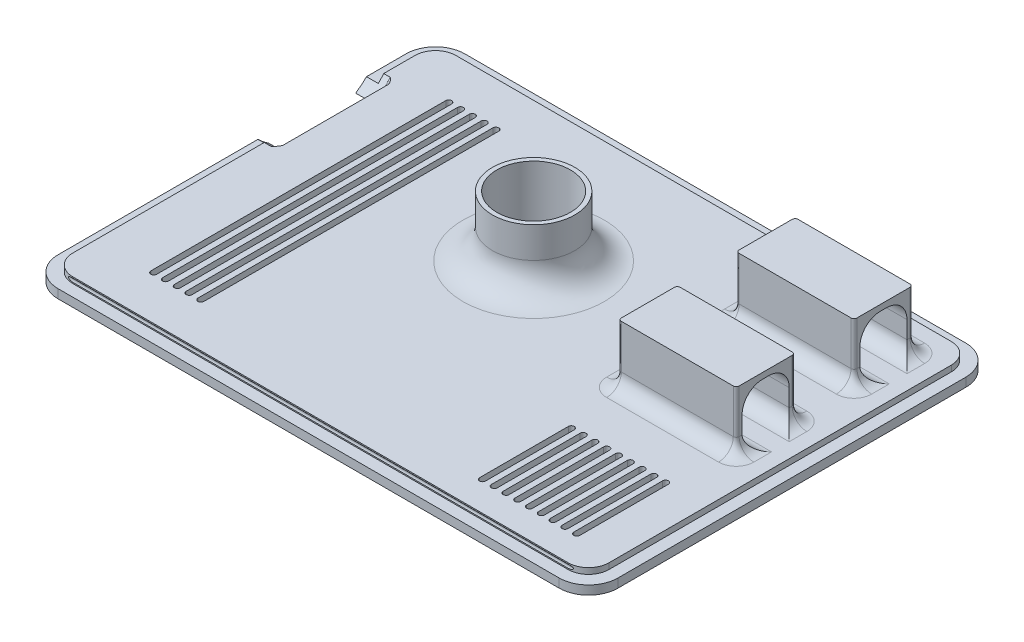
SolidWorks part; units mm, degrees
ref_plane "Front Plane" through (0, 0, 0) normal (0, 0, 1) x (1, 0, 0)
ref_plane "Top Plane" through (0, 0, 0) normal (0, 1, 0) x (1, 0, 0)
ref_plane "Right Plane" through (0, 0, 0) normal (1, 0, 0) x (0, 0, -1)
sketch "Sketch1" plane through (0, 0, 0) normal (0, 1, 0) x (1, 0, 0)
  line L0 (-95.075, -69.075) -> (95.075, -69.075)
  line L7 (95.075, -69.075) -> (95.075, 69.075)
  line L8 (-95.075, 69.075) -> (95.075, 69.075)
  line L9 (-95.075, -69.075) -> (-95.075, 69.075)
  point P0 (0, 69.075)
  point P2 (-95.075, 0)
  dimension "D1" = 138.15
  dimension "D2" = 190.15
extrude "Lid" add sketch "Sketch1" along normal blind 3
sketch "Sketch2" plane through (0, 3, 0) normal (0, 1, 0) x (1, 0, 0)
  line L0 (-91.075, 65.075) -> (-91.075, -65.075)
  line L1 (-91.075, -65.075) -> (91.075, -65.075)
  line L2 (91.075, -65.075) -> (91.075, 65.075)
  line L3 (91.075, 65.075) -> (-91.075, 65.075)
  line L4 (-95.075, 69.075) -> (-95.075, -69.075)
  line L5 (-95.075, -69.075) -> (95.075, -69.075)
  line L6 (95.075, -69.075) -> (95.075, 69.075)
  line L7 (95.075, 69.075) -> (-95.075, 69.075)
  line L8 (-95.075, 69.075) -> (-95.075, -69.075)
  line L9 (-95.075, -69.075) -> (95.075, -69.075)
  line L10 (95.075, -69.075) -> (95.075, 69.075)
  line L11 (95.075, 69.075) -> (-95.075, 69.075)
  dimension "D1" = 0
  dimension "D2" = 4
extrude "Insert" add sketch "Sketch2" along normal blind 2 contours L0 L1 L2 L3
sketch "Sketch3" plane through (0, 5, 0) normal (0, 1, 0) x (1, 0, 0)
  line L1 (41.075, 35.075) -> (81.075, 35.075)
  line L2 (41.075, 35.075) -> (41.075, 55.075)
  line L3 (41.075, 55.075) -> (81.075, 55.075)
  line L4 (91.075, 65.075) -> (-91.075, 65.075)
  line L5 (-91.075, 65.075) -> (-91.075, -65.075)
  line L6 (-91.075, -65.075) -> (91.075, -65.075)
  line L7 (91.075, -65.075) -> (91.075, 65.075)
  line L8 (91.075, 65.075) -> (-91.075, 65.075)
  line L9 (-91.075, 65.075) -> (-91.075, -65.075)
  line L10 (-91.075, -65.075) -> (91.075, -65.075)
  line L11 (91.075, -65.075) -> (91.075, 65.075)
  line L12 (81.075, 35.075) -> (81.075, 55.075)
  line L13 (41.075, 35.075) -> (81.075, 55.075) construction
  line L14 (41.075, 55.075) -> (81.075, 35.075) construction
  line L15 (41.075, 15.075) -> (81.075, 15.075)
  line L16 (41.075, 15.075) -> (41.075, -4.925)
  line L17 (41.075, -4.925) -> (81.075, -4.925)
  line L18 (81.075, 15.075) -> (81.075, -4.925)
  line L19 (41.075, 15.075) -> (81.075, -4.925) construction
  line L20 (41.075, -4.925) -> (81.075, 15.075) construction
  point P2 (61.075, 45.075)
  point P17 (61.075, 5.075)
  dimension "D2" = 10
  dimension "D3" = 50
  dimension "D4" = 10
  dimension "D5" = 30
  dimension "D6" = 50
  dimension "D7" = 70
  dimension "D1" = 0
extrude "Battery Contacts" add sketch "Sketch3" along normal blind 19.9 contours L2 L1 L12 L3 | L16 L15 L18 L17
sketch "Sketch9" plane through (81.075, 0, 0) normal (1, 0, 0) x (0, 0, -1)
  line L0 (-4.925, 5) -> (15.075, 5) construction
  line L1 (53.075, 5) -> (53.075, 15.9)
  line L2 (15.075, 24.9) -> (-4.925, 24.9) construction
  line L3 (53.075, 5) -> (37.075, 5)
  line L4 (35.075, 5) -> (55.075, 5) construction
  line L5 (37.075, 5) -> (37.075, 15.9)
  line L6 (55.075, 24.9) -> (35.075, 24.9) construction
  line L7 (46.075, 22.9) -> (44.075, 22.9)
  line L8 (-4.925, 5) -> (15.075, 5)
  line L9 (15.075, 5) -> (15.075, 24.9)
  line L10 (15.075, 24.9) -> (-4.925, 24.9)
  line L11 (-4.925, 24.9) -> (-4.925, 5)
  line L12 (35.075, 5) -> (55.075, 5)
  line L13 (55.075, 5) -> (55.075, 24.9)
  line L14 (55.075, 24.9) -> (35.075, 24.9)
  line L15 (35.075, 24.9) -> (35.075, 5)
  line L16 (-65.075, 5) -> (65.075, 5) construction
  line L17 (-2.925, 5) -> (13.075, 5)
  line L18 (-2.925, 5) -> (-2.925, 15.9)
  line L19 (4.075, 22.9) -> (6.075, 22.9)
  line L20 (13.075, 5) -> (13.075, 15.9)
  line L21 (25.075, -986.7231) -> (25.075, 49013.2769) construction
  line L22 (53.075, 5) -> (53.075, 15.9)
  arc A0 (-2.925, 15.9) -> (4.075, 22.9) centre (4.075, 15.9) cw
  arc A1 (6.075, 22.9) -> (13.075, 15.9) centre (6.075, 15.9) cw
  arc A2 (53.075, 15.9) -> (46.075, 22.9) centre (46.075, 15.9) ccw
  arc A3 (44.075, 22.9) -> (37.075, 15.9) centre (44.075, 15.9) ccw
  dimension "D1" = 2
  dimension "D2" = 2
  dimension "D3" = 2
  dimension "D4" = 2
  dimension "D5" = 10
extrude "Contact Lighteners" cut sketch "Sketch9" against normal up to next contours A1 L19 A0 L18 L8 L20 | L7 A3 L5 L3 L1 A2 region at (81.075, 13.3646, -45.075) region at (81.075, 13.3646, -5.075)
sketch "Sketch4" plane through (0, 5, 0) normal (0, 1, 0) x (1, 0, 0)
  line L1 (-22.275, 29.625) -> (1.225, 29.625) construction
  line L2 (-22.275, 29.625) -> (-22.275, 6.125) construction
  line L3 (-22.275, 6.125) -> (1.225, 6.125) construction
  line L4 (91.075, 65.075) -> (-91.075, 65.075)
  line L5 (-91.075, 65.075) -> (-91.075, -65.075)
  line L6 (-91.075, -65.075) -> (91.075, -65.075)
  line L7 (91.075, -65.075) -> (91.075, 65.075)
  line L8 (91.075, 65.075) -> (-91.075, 65.075)
  line L9 (-91.075, 65.075) -> (-91.075, -65.075)
  line L10 (-91.075, -65.075) -> (91.075, -65.075)
  line L11 (91.075, -65.075) -> (91.075, 65.075)
  line L12 (1.225, 29.625) -> (1.225, 6.125) construction
  line L13 (-22.275, 29.625) -> (1.225, 6.125) construction
  line L14 (-22.275, 6.125) -> (1.225, 29.625) construction
  line L566 (-10.525, 28.875) -> (-10.525, 6.875) construction
  line L567 (-9.775, 28.875) -> (-9.775, 6.875)
  line L568 (-63.575, 50.075) -> (-63.575, -50.075) construction
  line L569 (-81.075, 50.075) -> (-46.075, 50.075) construction
  line L570 (-81.075, 50.075) -> (-81.075, -50.075) construction
  line L571 (-81.075, -50.075) -> (-46.075, -50.075) construction
  line L572 (-46.075, 50.075) -> (-46.075, -50.075) construction
  line L573 (-62.575, 50.075) -> (-62.575, -50.075)
  line L574 (-64.575, 50.075) -> (-64.575, -50.075)
  line L575 (-59.575, 50.075) -> (-59.575, -50.075) construction
  line L576 (-58.575, 50.075) -> (-58.575, -50.075)
  line L577 (-60.575, 50.075) -> (-60.575, -50.075)
  line L578 (-55.575, 50.075) -> (-55.575, -50.075) construction
  line L579 (-54.575, 50.075) -> (-54.575, -50.075)
  line L580 (-56.575, 50.075) -> (-56.575, -50.075)
  line L581 (-67.575, 50.075) -> (-67.575, -50.075) construction
  line L582 (-11.275, 28.875) -> (-11.275, 6.875)
  line L583 (-7.525, 28.875) -> (-7.525, 6.875) construction
  line L584 (-6.775, 28.875) -> (-6.775, 6.875)
  line L585 (-8.275, 28.875) -> (-8.275, 6.875)
  line L586 (-4.525, 27.9776) -> (-4.525, 7.7724) construction
  line L587 (-3.775, 27.4927) -> (-3.775, 8.2573)
  line L588 (-5.275, 28.3869) -> (-5.275, 7.3631)
  line L589 (-66.575, 50.075) -> (-66.575, -50.075)
  line L590 (-68.575, 50.075) -> (-68.575, -50.075)
  line L591 (-63.575, 50.075) -> (-63.575, -50.075) construction
  line L592 (-62.575, 50.075) -> (-62.575, -50.075)
  line L593 (-64.575, 50.075) -> (-64.575, -50.075)
  line L594 (-71.575, 50.075) -> (-71.575, -50.075) construction
  line L595 (-70.575, 50.075) -> (-70.575, -50.075)
  line L596 (-72.575, 50.075) -> (-72.575, -50.075)
  line L597 (41.075, -4.925) -> (81.075, -4.925) construction
  line L598 (41.075, -55.075) -> (81.075, -55.075) construction
  line L599 (41.075, -55.075) -> (41.075, -24.925) construction
  line L600 (41.075, -24.925) -> (81.075, -24.925) construction
  line L601 (81.075, -55.075) -> (81.075, -24.925) construction
  line L602 (61.075, -24.925) -> (61.075, -55.075) construction
  line L603 (62.075, -24.925) -> (62.075, -55.075)
  line L604 (60.075, -24.925) -> (60.075, -55.075)
  line L605 (65.075, -24.925) -> (65.075, -55.075) construction
  line L606 (66.075, -24.925) -> (66.075, -55.075)
  line L607 (-1.525, 25.429) -> (-1.525, 10.321) construction
  line L608 (-0.775, 24.4324) -> (-0.775, 11.3176)
  line L609 (-2.275, 26.2416) -> (-2.275, 9.5084)
  line L610 (64.075, -24.925) -> (64.075, -55.075)
  line L611 (69.075, -24.925) -> (69.075, -55.075) construction
  line L612 (70.075, -24.925) -> (70.075, -55.075)
  line L613 (68.075, -24.925) -> (68.075, -55.075)
  line L614 (73.075, -24.925) -> (73.075, -55.075) construction
  line L615 (74.075, -24.925) -> (74.075, -55.075)
  line L616 (72.075, -24.925) -> (72.075, -55.075)
  line L617 (77.075, -24.925) -> (77.075, -55.075) construction
  line L618 (78.075, -24.925) -> (78.075, -55.075)
  line L619 (76.075, -24.925) -> (76.075, -55.075)
  line L620 (49.075, -24.925) -> (49.075, -55.075) construction
  line L621 (50.075, -24.925) -> (50.075, -55.075)
  line L622 (48.075, -24.925) -> (48.075, -55.075)
  line L623 (53.075, -24.925) -> (53.075, -55.075) construction
  line L625 (0.725, 21.2662) -> (0.725, 14.4838)
  line L626 (-19.525, 25.429) -> (-19.525, 10.321) construction
  line L627 (-18.775, 26.2416) -> (-18.775, 9.5084)
  line L628 (54.075, -24.925) -> (54.075, -55.075)
  line L629 (52.075, -24.925) -> (52.075, -55.075)
  line L630 (57.075, -24.925) -> (57.075, -55.075) construction
  line L631 (58.075, -24.925) -> (58.075, -55.075)
  line L632 (56.075, -24.925) -> (56.075, -55.075)
  line L634 (-16.525, 27.9776) -> (-16.525, 7.7724) construction
  line L635 (-15.775, 28.3869) -> (-15.775, 7.3631)
  line L636 (-17.275, 27.4927) -> (-17.275, 8.2573)
  line L637 (61.075, -24.925) -> (61.075, -55.075) construction
  line L638 (-13.525, 28.875) -> (-13.525, 6.875) construction
  line L639 (-12.775, 28.875) -> (-12.775, 6.875)
  line L640 (-14.275, 28.875) -> (-14.275, 6.875)
  line L641 (-10.525, 28.875) -> (-10.525, 6.875) construction
  line L642 (62.075, -24.925) -> (62.075, -55.075)
  line L643 (60.075, -24.925) -> (60.075, -55.075)
  line L644 (45.075, -24.925) -> (45.075, -55.075) construction
  line L645 (46.075, -24.925) -> (46.075, -55.075)
  line L646 (44.075, -24.925) -> (44.075, -55.075)
  line L647 (95.075, 69.075) -> (-95.075, 69.075) construction
  line L649 (95.075, -69.075) -> (95.075, 69.075) construction
  line L655 (-9.775, 28.875) -> (-9.775, 6.875)
  line L657 (-11.275, 28.875) -> (-11.275, 6.875)
  line L659 (-21.775, 21.2662) -> (-21.775, 14.4838)
  line L667 (-20.275, 24.4324) -> (-20.275, 11.3176)
  line L1107 (-1.525, 28.875) -> (-1.525, 6.875) construction
  line L1108 (-0.775, 28.875) -> (-0.775, 6.875)
  line L1109 (-2.275, 28.875) -> (-2.275, 6.875)
  line L1110 (-19.525, 28.875) -> (-19.525, 6.875) construction
  line L1111 (-18.775, 28.875) -> (-18.775, 6.875)
  line L1112 (-20.275, 28.875) -> (-20.275, 6.875)
  line L1113 (-16.525, 28.875) -> (-16.525, 6.875) construction
  line L1114 (-15.775, 28.875) -> (-15.775, 6.875)
  line L1115 (-17.275, 28.875) -> (-17.275, 6.875)
  line L1116 (-13.525, 28.875) -> (-13.525, 6.875) construction
  line L1117 (-12.775, 28.875) -> (-12.775, 6.875)
  line L1118 (-14.275, 28.875) -> (-14.275, 6.875)
  line L1119 (-22.525, 28.875) -> (-22.525, 6.875) construction
  line L1120 (-21.775, 28.875) -> (-21.775, 6.875)
  line L1121 (-23.275, 28.875) -> (-23.275, 6.875)
  line L1122 (-4.525, 28.875) -> (-4.525, 6.875) construction
  line L1123 (-3.775, 28.875) -> (-3.775, 6.875)
  line L1124 (-5.275, 28.875) -> (-5.275, 6.875)
  line L1125 (-7.525, 28.875) -> (-7.525, 6.875) construction
  line L1126 (-6.775, 28.875) -> (-6.775, 6.875)
  line L1127 (-8.275, 28.875) -> (-8.275, 6.875)
  line L1128 (1.475, 28.875) -> (1.475, 6.875) construction
  line L1129 (2.225, 28.875) -> (2.225, 6.875)
  line L1130 (0.725, 28.875) -> (0.725, 6.875)
  line L1131 (-1.525, 28.875) -> (-1.525, 6.875) construction
  line L1132 (-0.775, 28.875) -> (-0.775, 6.875)
  line L1133 (-2.275, 28.875) -> (-2.275, 6.875)
  line L1134 (-19.525, 28.875) -> (-19.525, 6.875) construction
  line L1135 (-18.775, 28.875) -> (-18.775, 6.875)
  line L1136 (-20.275, 28.875) -> (-20.275, 6.875)
  line L1137 (-16.525, 28.875) -> (-16.525, 6.875) construction
  line L1138 (-15.775, 28.875) -> (-15.775, 6.875)
  line L1139 (-17.275, 28.875) -> (-17.275, 6.875)
  line L1140 (-13.525, 28.875) -> (-13.525, 6.875) construction
  line L1141 (-12.775, 28.875) -> (-12.775, 6.875)
  line L1142 (-14.275, 28.875) -> (-14.275, 6.875)
  line L1143 (-22.525, 28.875) -> (-22.525, 6.875) construction
  line L1144 (-21.775, 28.875) -> (-21.775, 6.875)
  line L1145 (-23.275, 28.875) -> (-23.275, 6.875)
  line L1146 (-4.525, 28.875) -> (-4.525, 6.875) construction
  line L1147 (-3.775, 28.875) -> (-3.775, 6.875)
  line L1148 (-5.275, 28.875) -> (-5.275, 6.875)
  line L1149 (-7.525, 28.875) -> (-7.525, 6.875) construction
  line L1150 (-6.775, 28.875) -> (-6.775, 6.875)
  line L1151 (-8.275, 28.875) -> (-8.275, 6.875)
  line L1152 (1.475, 28.875) -> (1.475, 6.875) construction
  line L1153 (2.225, 28.875) -> (2.225, 6.875)
  line L1154 (0.725, 28.875) -> (0.725, 6.875)
  circle A12 centre (-10.525, 17.875) radius 11.75
  arc A13 (-9.775, 28.875) -> (-11.275, 28.875) centre (-10.525, 28.875) ccw
  arc A14 (-11.275, 6.875) -> (-9.775, 6.875) centre (-10.525, 6.875) ccw
  arc A15 (-6.775, 28.875) -> (-6.7882, 29.015) centre (-7.525, 28.875) ccw
  arc A16 (-8.275, 6.875) -> (-8.0887, 6.3803) centre (-7.525, 6.875) ccw
  arc A27 (-12.775, 28.875) -> (-12.9613, 29.3697) centre (-13.525, 28.875) ccw
  arc A28 (-14.275, 6.875) -> (-14.2618, 6.735) centre (-13.525, 6.875) ccw
  arc A29 (-9.775, 28.875) -> (-11.275, 28.875) centre (-10.525, 28.875) ccw
  arc A30 (-11.275, 6.875) -> (-9.775, 6.875) centre (-10.525, 6.875) ccw
  arc A33 (-62.575, 50.075) -> (-64.575, 50.075) centre (-63.575, 50.075) ccw
  arc A34 (-64.575, -50.075) -> (-62.575, -50.075) centre (-63.575, -50.075) ccw
  arc A35 (-58.575, 50.075) -> (-60.575, 50.075) centre (-59.575, 50.075) ccw
  arc A36 (-60.575, -50.075) -> (-58.575, -50.075) centre (-59.575, -50.075) ccw
  arc A37 (-54.575, 50.075) -> (-56.575, 50.075) centre (-55.575, 50.075) ccw
  arc A38 (-56.575, -50.075) -> (-54.575, -50.075) centre (-55.575, -50.075) ccw
  arc A39 (-14.2618, 29.015) -> (-14.275, 28.875) centre (-13.525, 28.875) ccw
  arc A40 (-66.575, 50.075) -> (-68.575, 50.075) centre (-67.575, 50.075) ccw
  arc A41 (-68.575, -50.075) -> (-66.575, -50.075) centre (-67.575, -50.075) ccw
  arc A42 (-12.9613, 6.3803) -> (-12.775, 6.875) centre (-13.525, 6.875) ccw
  arc A43 (-62.575, 50.075) -> (-64.575, 50.075) centre (-63.575, 50.075) ccw
  arc A44 (-64.575, -50.075) -> (-62.575, -50.075) centre (-63.575, -50.075) ccw
  arc A45 (-70.575, 50.075) -> (-72.575, 50.075) centre (-71.575, 50.075) ccw
  arc A46 (-72.575, -50.075) -> (-70.575, -50.075) centre (-71.575, -50.075) ccw
  arc A47 (62.075, -24.925) -> (60.075, -24.925) centre (61.075, -24.925) ccw
  arc A48 (60.075, -55.075) -> (62.075, -55.075) centre (61.075, -55.075) ccw
  arc A49 (-6.7882, 6.735) -> (-6.775, 6.875) centre (-7.525, 6.875) ccw
  arc A50 (66.075, -24.925) -> (64.075, -24.925) centre (65.075, -24.925) ccw
  arc A51 (64.075, -55.075) -> (66.075, -55.075) centre (65.075, -55.075) ccw
  arc A52 (-8.0887, 29.3697) -> (-8.275, 28.875) centre (-7.525, 28.875) ccw
  arc A53 (70.075, -24.925) -> (68.075, -24.925) centre (69.075, -24.925) ccw
  arc A54 (68.075, -55.075) -> (70.075, -55.075) centre (69.075, -55.075) ccw
  arc A55 (74.075, -24.925) -> (72.075, -24.925) centre (73.075, -24.925) ccw
  arc A56 (72.075, -55.075) -> (74.075, -55.075) centre (73.075, -55.075) ccw
  arc A57 (78.075, -24.925) -> (76.075, -24.925) centre (77.075, -24.925) ccw
  arc A58 (76.075, -55.075) -> (78.075, -55.075) centre (77.075, -55.075) ccw
  arc A59 (50.075, -24.925) -> (48.075, -24.925) centre (49.075, -24.925) ccw
  arc A60 (48.075, -55.075) -> (50.075, -55.075) centre (49.075, -55.075) ccw
  arc A61 (54.075, -24.925) -> (52.075, -24.925) centre (53.075, -24.925) ccw
  arc A62 (52.075, -55.075) -> (54.075, -55.075) centre (53.075, -55.075) ccw
  arc A63 (58.075, -24.925) -> (56.075, -24.925) centre (57.075, -24.925) ccw
  arc A64 (56.075, -55.075) -> (58.075, -55.075) centre (57.075, -55.075) ccw
  arc A65 (62.075, -24.925) -> (60.075, -24.925) centre (61.075, -24.925) ccw
  arc A66 (60.075, -55.075) -> (62.075, -55.075) centre (61.075, -55.075) ccw
  arc A67 (46.075, -24.925) -> (44.075, -24.925) centre (45.075, -24.925) ccw
  arc A68 (44.075, -55.075) -> (46.075, -55.075) centre (45.075, -55.075) ccw
  arc A325 (-0.775, 28.875) -> (-2.275, 28.875) centre (-1.525, 28.875) ccw
  arc A326 (-2.275, 6.875) -> (-0.775, 6.875) centre (-1.525, 6.875) ccw
  arc A327 (-18.775, 28.875) -> (-20.275, 28.875) centre (-19.525, 28.875) ccw
  arc A328 (-20.275, 6.875) -> (-18.775, 6.875) centre (-19.525, 6.875) ccw
  arc A329 (-15.775, 28.875) -> (-17.275, 28.875) centre (-16.525, 28.875) ccw
  arc A330 (-17.275, 6.875) -> (-15.775, 6.875) centre (-16.525, 6.875) ccw
  arc A331 (-12.775, 28.875) -> (-14.275, 28.875) centre (-13.525, 28.875) ccw
  arc A332 (-14.275, 6.875) -> (-12.775, 6.875) centre (-13.525, 6.875) ccw
  arc A333 (-21.775, 28.875) -> (-23.275, 28.875) centre (-22.525, 28.875) ccw
  arc A334 (-23.275, 6.875) -> (-21.775, 6.875) centre (-22.525, 6.875) ccw
  arc A335 (-3.775, 28.875) -> (-5.275, 28.875) centre (-4.525, 28.875) ccw
  arc A336 (-5.275, 6.875) -> (-3.775, 6.875) centre (-4.525, 6.875) ccw
  arc A337 (-6.775, 28.875) -> (-8.275, 28.875) centre (-7.525, 28.875) ccw
  arc A338 (-8.275, 6.875) -> (-6.775, 6.875) centre (-7.525, 6.875) ccw
  arc A339 (2.225, 28.875) -> (0.725, 28.875) centre (1.475, 28.875) ccw
  arc A340 (0.725, 6.875) -> (2.225, 6.875) centre (1.475, 6.875) ccw
  point P2 (-10.525, 17.875)
  point P21 (-10.525, 17.875)
  point P30 (-5.675, 22.825)
  point P31 (-17.675, 22.825)
  point P38 (-2.675, 22.825)
  point P45 (0.325, 22.825)
  point P52 (3.325, 22.825)
  point P59 (-17.675, 22.825)
  point P60 (-63.575, 0)
  point P62 (-14.675, 22.825)
  point P66 (-14.675, 22.825)
  point P73 (-11.675, 22.825)
  point P80 (-10.525, 17.875)
  point P87 (-20.675, 22.825)
  point P91 (0.325, 22.825)
  point P99 (-59.575, 0)
  point P104 (-11.675, 22.825)
  point P109 (-55.575, 0)
  point P114 (-20.675, 22.825)
  point P121 (-67.575, 0)
  point P126 (-2.675, 22.825)
  point P129 (-63.575, 0)
  point P133 (-5.675, 22.825)
  point P137 (-71.575, 0)
  point P142 (3.325, 22.825)
  point P151 (61.075, -40)
  point P160 (65.075, -40)
  point P167 (69.075, -40)
  point P174 (73.075, -40)
  point P181 (77.075, -40)
  point P188 (49.075, -40)
  point P195 (53.075, -40)
  point P202 (57.075, -40)
  point P209 (61.075, -40)
  point P216 (45.075, -40)
  point P825 (0.325, 22.825)
  point P832 (-17.675, 22.825)
  point P839 (-14.675, 22.825)
  point P846 (-11.675, 22.825)
  point P853 (-20.675, 22.825)
  point P860 (-2.675, 22.825)
  point P867 (-5.675, 22.825)
  point P874 (3.325, 22.825)
  point P881 (0.325, 22.825)
  point P888 (-17.675, 22.825)
  point P895 (-14.675, 22.825)
  point P902 (-11.675, 22.825)
  point P909 (-20.675, 22.825)
  point P916 (-2.675, 22.825)
  point P923 (-5.675, 22.825)
  point P930 (3.325, 22.825)
  point P937 (0.325, 22.825)
  point P944 (-17.675, 22.825)
  point P951 (-14.675, 22.825)
  point P958 (-11.675, 22.825)
  point P965 (-20.675, 22.825)
  point P972 (-2.675, 22.825)
  point P979 (-5.675, 22.825)
  point P986 (3.325, 22.825)
  point P993 (0.325, 22.825)
  point P1000 (-17.675, 22.825)
  point P1007 (-14.675, 22.825)
  point P1014 (-11.675, 22.825)
  point P1021 (-20.675, 22.825)
  point P1028 (-2.675, 22.825)
  point P1035 (-5.675, 22.825)
  point P1042 (3.325, 22.825)
  point P1049 (0.325, 22.825)
  point P1056 (-17.675, 22.825)
  point P1063 (-14.675, 22.825)
  point P1070 (-11.675, 22.825)
  point P1077 (-20.675, 22.825)
  point P1084 (-2.675, 22.825)
  point P1091 (-5.675, 22.825)
  point P1098 (3.325, 22.825)
  point P1105 (0.325, 22.825)
  point P1112 (-17.675, 22.825)
  point P1119 (-14.675, 22.825)
  point P1126 (-11.675, 22.825)
  point P1133 (-20.675, 22.825)
  point P1140 (-2.675, 22.825)
  point P1147 (-5.675, 22.825)
  point P1154 (3.325, 22.825)
  point P1161 (0.325, 22.825)
  point P1168 (-17.675, 22.825)
  point P1175 (-14.675, 22.825)
  point P1182 (-11.675, 22.825)
  point P1189 (-20.675, 22.825)
  point P1196 (-2.675, 22.825)
  point P1203 (-5.675, 22.825)
  point P1210 (3.325, 22.825)
  point P1217 (-1.525, 17.875)
  point P1224 (-19.525, 17.875)
  point P1231 (-16.525, 17.875)
  point P1238 (-13.525, 17.875)
  point P1245 (-22.525, 17.875)
  point P1252 (-4.525, 17.875)
  point P1259 (-7.525, 17.875)
  point P1266 (1.475, 17.875)
  point P1273 (-1.525, 17.875)
  point P1280 (-19.525, 17.875)
  point P1287 (-16.525, 17.875)
  point P1294 (-13.525, 17.875)
  point P1301 (-22.525, 17.875)
  point P1308 (-4.525, 17.875)
  point P1315 (-7.525, 17.875)
  point P1322 (1.475, 17.875)
  point P1329 (-1.525, 17.875)
  point P1336 (-19.525, 17.875)
  point P1343 (-16.525, 17.875)
  point P1350 (-13.525, 17.875)
  point P1357 (-22.525, 17.875)
  point P1364 (-4.525, 17.875)
  point P1371 (-7.525, 17.875)
  point P1378 (1.475, 17.875)
  point P1385 (-1.525, 17.875)
  point P1392 (-19.525, 17.875)
  point P1399 (-16.525, 17.875)
  point P1406 (-13.525, 17.875)
  point P1413 (-22.525, 17.875)
  point P1420 (-4.525, 17.875)
  point P1427 (-7.525, 17.875)
  point P1434 (1.475, 17.875)
  point P1441 (-1.525, 17.875)
  point P1448 (-19.525, 17.875)
  point P1455 (-16.525, 17.875)
  point P1462 (-13.525, 17.875)
  point P1469 (-22.525, 17.875)
  point P1476 (-4.525, 17.875)
  point P1483 (-7.525, 17.875)
  point P1490 (1.475, 17.875)
  point P1497 (-1.525, 17.875)
  point P1504 (-19.525, 17.875)
  point P1511 (-16.525, 17.875)
  point P1518 (-13.525, 17.875)
  point P1525 (-22.525, 17.875)
  point P1532 (-4.525, 17.875)
  point P1539 (-7.525, 17.875)
  point P1546 (1.475, 17.875)
  point P1553 (-1.525, 17.875)
  point P1560 (-19.525, 17.875)
  point P1567 (-16.525, 17.875)
  point P1574 (-13.525, 17.875)
  point P1581 (-22.525, 17.875)
  point P1588 (-4.525, 17.875)
  point P1595 (-7.525, 17.875)
  point P1602 (1.475, 17.875)
  point P1609 (-1.525, 17.875)
  point P1616 (-19.525, 17.875)
  point P1623 (-16.525, 17.875)
  point P1630 (-13.525, 17.875)
  point P1637 (-22.525, 17.875)
  point P1644 (-4.525, 17.875)
  point P1651 (-7.525, 17.875)
  point P1658 (1.475, 17.875)
  point P1665 (-1.525, 17.875)
  point P1672 (-19.525, 17.875)
  point P1679 (-16.525, 17.875)
  point P1686 (-13.525, 17.875)
  point P1693 (-22.525, 17.875)
  point P1700 (-4.525, 17.875)
  point P1707 (-7.525, 17.875)
  point P1714 (1.475, 17.875)
  point P1721 (-1.525, 17.875)
  point P1728 (-19.525, 17.875)
  point P1735 (-16.525, 17.875)
  point P1742 (-13.525, 17.875)
  point P1749 (-22.525, 17.875)
  point P1756 (-4.525, 17.875)
  point P1763 (-7.525, 17.875)
  point P1770 (1.475, 17.875)
  point P1777 (-1.525, 17.875)
  point P1784 (-19.525, 17.875)
  point P1791 (-16.525, 17.875)
  point P1798 (-13.525, 17.875)
  point P1805 (-22.525, 17.875)
  point P1812 (-4.525, 17.875)
  point P1819 (-7.525, 17.875)
  point P1826 (1.475, 17.875)
  dimension "D3" = 23.5
  dimension "D4" = 51.2
  dimension "D5" = 1.5
  dimension "D6" = 2
  dimension "D7" = 5
  dimension "D8" = 1.5
  dimension "D9" = 1.5
  dimension "D10" = 15
  dimension "D11" = 15
  dimension "D12" = 10
  dimension "D13" = 45
  dimension "D14" = 2
  dimension "D15" = 2
  dimension "D16" = 3
  dimension "D17" = 2
  dimension "D18" = 10
  dimension "D19" = 10
  dimension "D20" = 20
  dimension "D21" = 50
  dimension "D22" = 2
  dimension "D23" = 2
  dimension "D24" = 5
  dimension "D25" = 2
  dimension "D26" = 105.6
  dimension "D1" = 0
extrude "Vent Holes" cut sketch "Sketch4" against normal through all contours L659 A12 | L627 A12 L667 | L635 A12 L636 | A12 A42 L639 A27 A39 L640 A28 | A14 L567 A13 L582 | A12 A52 L585 A16 A49 L584 A15 | L588 A12 L587 | L609 A12 L608 | L625 A12 | L645 A68 L646 A67 | L621 A60 L622 A59 | L628 A62 L629 A61 | L631 A64 L632 A63 | L604 A48 L603 A47 | L606 A51 L610 A50 | L612 A54 L613 A53 | L615 A56 L616 A55 | L618 A58 L619 A57 | L595 A46 L596 A45 | L589 A41 L590 A40 | L592 A44 L593 A43 | L576 A36 L577 A35 | L579 A38 L580 A37 region at (-10.525, 5, -17.875) region at (-7.5281, 5, -17.875) region at (-13.5219, 5, -17.875) region at (-4.5361, 5, -17.875) region at (-16.5139, 5, -17.875) region at (-1.5549, 5, -17.875) region at (-19.4951, 5, -17.875) region at (0.9254, 5, -17.875) region at (-21.9754, 5, -17.875)
fillet "Fillet1" radius 10 4 edges at (95.075, 1.5, -69.075) (95.075, 1.5, 69.075) (-95.075, 1.5, -69.075) (-95.075, 1.5, 69.075)
fillet "Fillet2" radius 6.95 4 edges at (-91.075, 4, -65.075) (91.075, 4, -65.075) (91.075, 4, 65.075) (-91.075, 4, 65.075)
sketch "Sketch5" plane through (91.075, 0, 0) normal (1, 0, 0) x (0, 0, -1)
  line L0 (-65.075, 3) -> (-65.075, 5) construction
  line L1 (-65.075, 4.6) -> (-65.075, 3.4)
  line L2 (65.075, 5) -> (65.075, 3) construction
  line L3 (65.075, 5) -> (58.125, 5) construction
  line L4 (65.075, 4.6) -> (65.075, 3.4)
  arc A0 (-65.075, 4.6) -> (-65.075, 3.4) centre (-65.875, 4) cw
  arc A1 (65.075, 4.6) -> (65.075, 3.4) centre (65.875, 4) ccw
  dimension "D3" = 1
  dimension "D6" = 1
  dimension "D1" = 0.4
  dimension "D2" = 0.4
  dimension "D4" = 0.4
  dimension "D5" = 1.2
extrude "Snap Groove" cut sketch "Sketch5" against normal through all
sketch "Sketch6" plane through (0, 5, 0) normal (0, 1, 0) x (1, 0, 0)
  line L4 (84.125, 65.075) -> (-84.125, 65.075)
  line L5 (-91.075, 58.125) -> (-91.075, -58.125)
  line L6 (-84.125, -65.075) -> (84.125, -65.075)
  line L7 (91.075, -58.125) -> (91.075, 58.125)
  line L8 (84.125, 65.075) -> (-84.125, 65.075)
  line L9 (-91.075, 58.125) -> (-91.075, -58.125)
  line L10 (-84.125, -65.075) -> (84.125, -65.075)
  line L11 (91.075, -58.125) -> (91.075, 58.125)
  circle A0 centre (-10.525, 17.875) radius 12.5
  circle A1 centre (-10.525, 17.875) radius 14
  arc A4 (-84.125, 65.075) -> (-91.075, 58.125) centre (-84.125, 58.125) ccw
  arc A5 (-91.075, -58.125) -> (-84.125, -65.075) centre (-84.125, -58.125) ccw
  arc A6 (84.125, -65.075) -> (91.075, -58.125) centre (84.125, -58.125) ccw
  arc A7 (91.075, 58.125) -> (84.125, 65.075) centre (84.125, 58.125) ccw
  arc A8 (-84.125, 65.075) -> (-91.075, 58.125) centre (-84.125, 58.125) ccw
  arc A9 (-91.075, -58.125) -> (-84.125, -65.075) centre (-84.125, -58.125) ccw
  arc A10 (84.125, -65.075) -> (91.075, -58.125) centre (84.125, -58.125) ccw
  arc A11 (91.075, 58.125) -> (84.125, 65.075) centre (84.125, 58.125) ccw
  dimension "D2" = 28
  dimension "D3" = 1.5
  dimension "D1" = 0
extrude "Cooling Guide" add sketch "Sketch6" along normal blind 20.5 contours A1 A0 region at (-24.129, 5, -17.875)
fillet "Fillet5" radius 10 1 edges at (-10.525, 5, -3.875)
sketch "Sketch8" plane through (-95.075, 0, 0) normal (-1, 0, 0) x (0, 0, 1)
  line L0 (-59.075, 3) -> (-59.075, 48) construction
  line L2 (-59.075, 3) -> (59.075, 3) construction
  line L5 (-27.225, 48) -> (-27.225, 21.9) construction
  circle A0 centre (-27.225, 21.9) radius 26.4
  dimension "D4" = 52.8
  dimension "D1" = 45
  dimension "D2" = 31.85
  dimension "D3" = 26.1
extrude "EDoF Insert" cut sketch "Sketch8" against normal blind 8
fillet "Fillet6" radius 1.8 2 edges at (-87.075, 2.3033, -9.5352) (-87.075, 2.3033, -44.9148) conic radius 7
fillet "Fillet7" radius 1 8 edges at (81.075, 14.95, -55.075) (81.075, 14.95, -35.075) (41.075, 14.95, -35.075) (41.075, 14.95, -55.075) (41.075, 14.95, -15.075) (41.075, 14.95, 4.925) (81.075, 14.95, 4.925) (81.075, 14.95, -15.075)
fillet "Fillet8" radius 5 24 edges at (41.075, 5, 3.425) (41.3679, 5, 4.6321) (81.075, 5, 3.425) (80.7821, 5, 4.6321) (41.075, 5, -36.575) (41.3679, 5, -35.3679) (81.075, 5, -36.575) (80.7821, 5, -35.3679) (41.075, 5, -53.575) (41.3679, 5, -54.7821) (81.075, 5, -53.575) (80.7821, 5, -54.7821) (41.075, 5, -13.575) (41.3679, 5, -14.7821) (81.075, 5, -13.575) (80.7821, 5, -14.7821) (61.075, 5, 4.925) (61.075, 5, -13.075) (61.075, 5, -35.075) (61.075, 5, -53.075) (61.075, 5, -37.075) (61.075, 5, 2.925) (61.075, 5, -55.075) (61.075, 5, -15.075)
